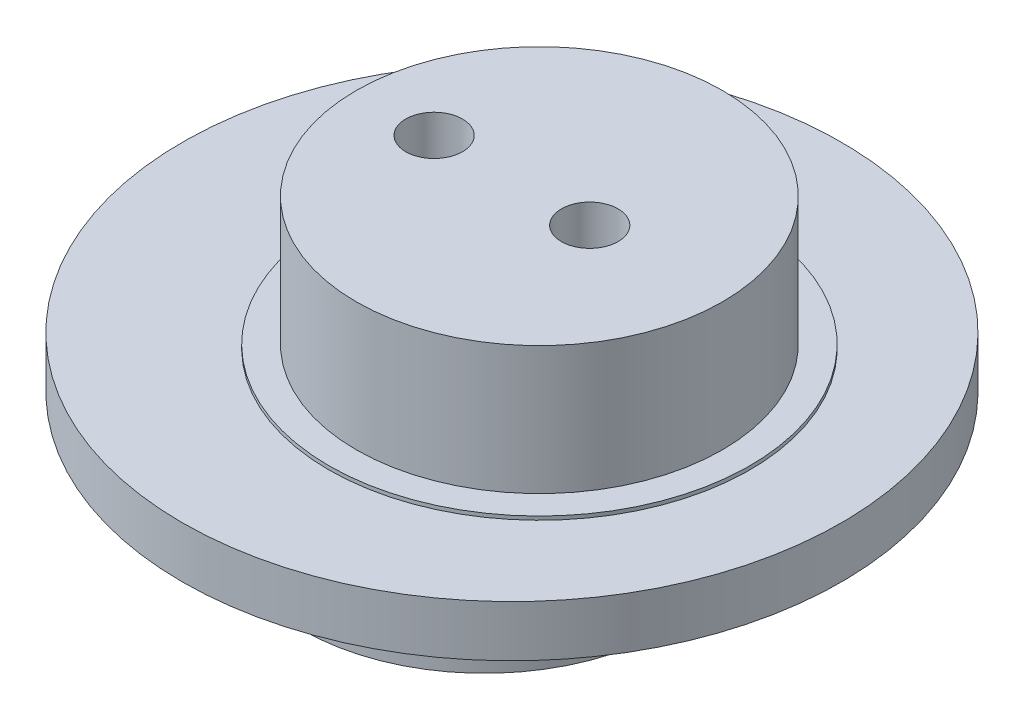
SolidWorks part; units mm, degrees
ref_plane "Ebene vorne" through (0, 0, 0) normal (0, 0, 1) x (1, 0, 0)
ref_plane "Ebene oben" through (0, 0, 0) normal (0, 1, 0) x (1, 0, 0)
ref_plane "Ebene rechts" through (0, 0, 0) normal (1, 0, 0) x (0, 0, -1)
sketch "Skizze1" plane through (0, 0, 0) normal (0, 1, 0) x (1, 0, 0)
  circle A0 centre (0, 0) radius 18
  dimension "D1" = 36
extrude "Aufsatz-Linear austragen1" add sketch "Skizze1" along normal blind 2.8
sketch "Skizze2" plane through (0, 2.8, 0) normal (0, 1, 0) x (1, 0, 0)
  line L0 (0, 0) -> (-50000, 0) construction
  circle A1 centre (1.5, 0) radius 11.5
  point P6 (0, 0)
  dimension "D1" = 1.5
  dimension "D2" = 23
extrude "Aufsatz-Linear austragen2" add sketch "Skizze2" along normal blind 0.2
sketch "Skizze3" plane through (0, 3, 0) normal (0, 1, 0) x (1, 0, 0)
  circle A0 centre (1.5, 0) radius 10
  dimension "D1" = 20
extrude "Aufsatz-Linear austragen3" add sketch "Skizze3" along normal blind 7
sketch "Skizze4" plane through (0, 0, 0) normal (0, -1, 0) x (1, 0, 0)
  line L0 (0, 0) -> (-50000, 0) construction
  circle A0 centre (-1.5, 0) radius 10
  point P5 (0, 0)
  point P6 (-0.9107, 0)
  dimension "D1" = 20
  dimension "D2" = 1.5
extrude "Aufsatz-Linear austragen4" add sketch "Skizze4" along normal blind 7
hole_wizard "Ø3.1 (3.1) Durchmesser Bohrung1" positions "Skizze5" profile "Skizze6" hole size "Ø3.1" standard "ISO" end condition through all
sketch "Skizze5" plane through (0, 10, 0) normal (0, 1, 0) x (1, 0, 0)
  line L0 (0, 0) -> (-50000, 0) construction
  line L1 (0, 0) -> (0, -50000) construction
  point P0 (4.25, 0)
  point P2 (-4.25, 0)
  point P11 (0, 0)
  dimension "D1" = 8.5
sketch "Skizze6" plane through (4.25, 10, 0) normal (1, 0, 0) x (0, 0, 1)
  line L0 (0, 0) -> (0, 17)
  line L1 (0, 17) -> (1.55, 17)
  line L2 (1.55, 17) -> (1.55, 0)
  line L5 (1.55, 0) -> (0, 0)
  line L11 (0, -6.35) -> (0, 107.95) construction
  dimension "Bohrerdurchmesser" = 3.1
  dimension "Bohrungstiefe" = 17
